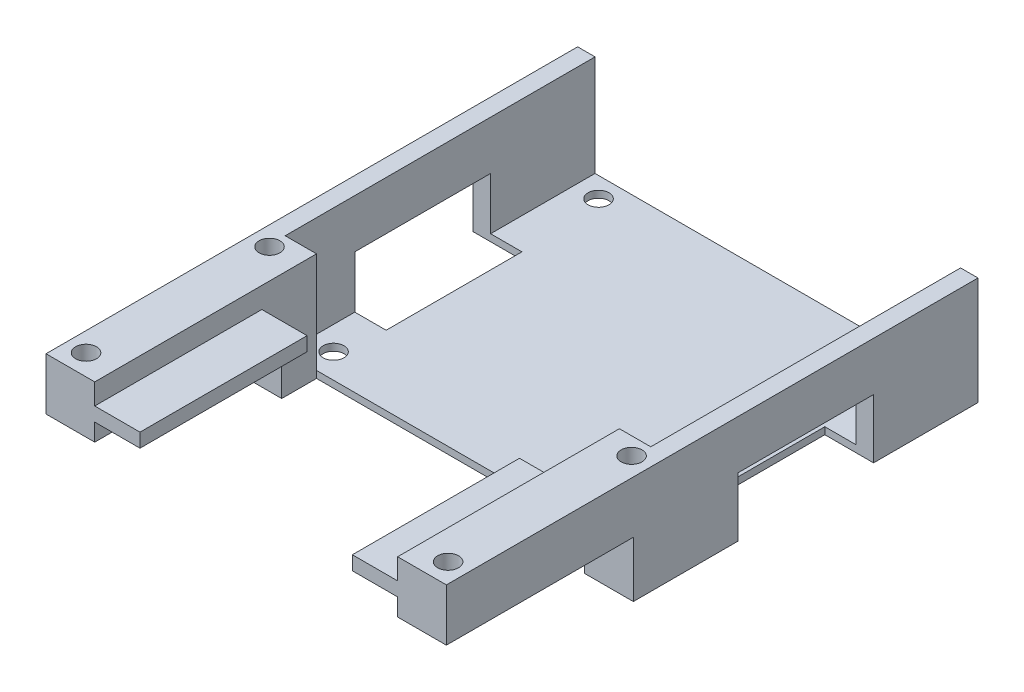
SolidWorks part; units mm, degrees
ref_plane "Front Plane" through (0, 0, 0) normal (0, 0, 1) x (1, 0, 0)
ref_plane "Top Plane" through (0, 0, 0) normal (0, 1, 0) x (1, 0, 0)
ref_plane "Right Plane" through (0, 0, 0) normal (1, 0, 0) x (0, 0, -1)
sketch "Sketch1" plane through (0, 0, 0) normal (0, 1, 0) x (1, 0, 0)
  line L0 (0, 0) -> (0, 76.35) construction
  line L1 (-28.75, 76.35) -> (28.75, 76.35)
  line L2 (28.75, 76.35) -> (28.75, 0)
  line L3 (28.75, 0) -> (21.75, 0)
  line L4 (21.75, 0) -> (21.75, 31.85)
  line L5 (21.75, 31.85) -> (-21.75, 31.85)
  line L6 (-21.75, 31.85) -> (-21.75, 0)
  line L7 (-21.75, 0) -> (-28.75, 0)
  line L8 (-28.75, 0) -> (-28.75, 76.35)
  line L9 (-26.25, 76.35) -> (-26.25, 31.85)
  line L14 (-26.25, 31.85) -> (-21.75, 31.85)
  line L15 (26.25, 76.35) -> (26.25, 31.85)
  line L16 (26.25, 31.85) -> (21.75, 31.85)
  line L17 (28.75, 74.35) -> (30.25, 74.35)
  line L18 (-28.75, 41.35) -> (-26.25, 41.35)
  line L19 (-28.75, 41.35) -> (-28.75, 53.35)
  line L20 (-28.75, 53.35) -> (-26.25, 53.35)
  line L21 (-26.25, 41.35) -> (-26.25, 53.35)
  line L22 (30.25, 68.35) -> (28.75, 68.35)
  line L23 (-30.25, 68.35) -> (-28.75, 68.35)
  line L24 (-28.75, 74.35) -> (-30.25, 74.35)
  arc A0 (30.25, 68.35) -> (30.25, 74.35) centre (30.25, 71.35) ccw
  arc A1 (-30.25, 68.35) -> (-30.25, 74.35) centre (-30.25, 71.35) cw
  point P10 (0, 76.35)
  point P16 (-27.5, 41.35)
  point P17 (-22.85, 73.45)
  point P18 (22.85, 73.45)
  point P23 (22.85, 35.4)
  point P24 (-22.85, 35.4)
  point P25 (26, 3)
  point P26 (26, 29.35)
  point P27 (-26, 29.35)
  point P28 (-26, 3)
  point P40 (30.25, 71.35)
  point P41 (-30.25, 71.35)
  dimension "D16" = 3
  dimension "D1" = 2.5
  dimension "D2" = 7
  dimension "D3" = 43.5
  dimension "D4" = 31.85
  dimension "D5" = 44.5
  dimension "D6" = 23
  dimension "D7" = 12
  dimension "D8" = 22.85
  dimension "D9" = 38.05
  dimension "D10" = 2.9
  dimension "D11" = 52
  dimension "D12" = 52
  dimension "D13" = 47
  dimension "D14" = 3
  dimension "D15" = 1.5
  dimension "D17" = 2
extrude "Boss-Extrude1" add sketch "Sketch1" along normal blind 1 contours L5 L0 L1 L9 L14 | L0 L5 L16 L15 L1 region at (-13.125, 0, -54.1) region at (13.125, 0, -54.1)
extrude "Boss-Extrude2" add sketch "Sketch1<3>" along normal blind 15.5 contours L18 L8 L7 L6 L14 L9 | L8 L20 L9 L1 | L15 L16 L4 L3 L2 L1 | L20 L8 L18 L9 region at (-27.5, 0, -64.85) region at (25.999, 0, -28.6329) region at (-27.5, 0, -47.35) region at (-25.4666, 0, -17.9154)
sketch "Sketch1<3>" plane through (0, 0, 0) normal (0, 1, 0) x (1, 0, 0) same geometry as "Sketch1"
hole_wizard "Ø3.0 (3) Diameter Hole1" positions "Sketch4" profile "Sketch5" hole size "Ø3.0" standard "ANSI Metric" end condition through all
sketch "Sketch4" plane through (0, 0, 0) normal (0, -1, 0) x (-1, 0, 0)
  point P0 (-22.85, 73.45)
  point P3 (22.85, 73.45)
  point P6 (26, 29.35)
  point P9 (22.85, 35.4)
  point P12 (-22.85, 35.4)
  point P15 (-26, 29.35)
  point P18 (-26, 3)
  point P21 (26, 3)
  point P24 (-30.25, 71.35)
  point P27 (30.25, 71.35)
sketch "Sketch5" plane through (22.85, 0, -73.45) normal (1, 0, 0) x (0, 0, -1)
  line L0 (0, 0) -> (0, 15.5)
  line L1 (0, 15.5) -> (1.5, 15.5)
  line L2 (1.5, 15.5) -> (1.5, 0)
  line L5 (1.5, 0) -> (0, 0)
  line L11 (0, -6.35) -> (0, 107.95) construction
  dimension "Thru Hole Dia." = 3
  dimension "Thru Hole Depth" = 15.5
sketch "Sketch6" plane through (0, 0, 0) normal (0, 0, 1) x (1, 0, 0)
  line L0 (-21.75, 15.5) -> (-21.75, 0) construction
  line L5 (0, -1.6497) -> (0, 21.9352) construction
  line L6 (-21.75, 10.5) -> (-15.25, 10.5)
  line L7 (-21.75, 10.5) -> (-21.75, 12.5)
  line L8 (-21.75, 12.5) -> (-15.25, 12.5)
  line L9 (-15.25, 10.5) -> (-15.25, 12.5)
  line L10 (-28.75, 15.5) -> (-28.75, 0) construction
  line L11 (-20.25, 10.5) -> (-21.75, 10.5)
  line L12 (-20.25, 10.5) -> (-20.25, 8)
  line L13 (-20.25, 8) -> (-21.75, 8)
  line L14 (-21.75, 10.5) -> (-21.75, 8)
  line L15 (-21.75, 0) -> (-28.75, 0)
  line L16 (-21.75, 0) -> (-21.75, 8)
  line L17 (-21.75, 8) -> (-28.75, 8)
  line L18 (-28.75, 0) -> (-28.75, 8)
  line L19 (28.75, 0) -> (28.75, 8)
  line L20 (21.75, 8) -> (28.75, 8)
  line L21 (21.75, 0) -> (21.75, 8)
  line L22 (21.75, 0) -> (28.75, 0)
  line L23 (21.75, 10.5) -> (21.75, 8)
  line L24 (20.25, 8) -> (21.75, 8)
  line L25 (20.25, 10.5) -> (20.25, 8)
  line L26 (20.25, 10.5) -> (21.75, 10.5)
  line L27 (15.25, 10.5) -> (15.25, 12.5)
  line L28 (21.75, 12.5) -> (15.25, 12.5)
  line L29 (21.75, 10.5) -> (21.75, 12.5)
  line L30 (21.75, 10.5) -> (15.25, 10.5)
  line L31 (-21.75, 15.5) -> (-28.75, 15.5) construction
  line M21 (21.75, 0) -> (28.75, 0)
  line M22 (28.75, 0) -> (28.75, 15.5)
  line M24 (21.75, 15.5) -> (21.75, 0)
  dimension "D1" = 6.5
  dimension "D2" = 3
  dimension "D3" = 2
  dimension "D4" = 2.5
  dimension "D5" = 1.5
extrude "Boss-Extrude3" add sketch "Sketch6" against normal blind 24 contours L30 L26 L28 L27 M24 | L6 L9 L8 L7 region at (-18.5, 11.5, 0) region at (18.5, 11.5, 0)
extrude "Cut-Extrude1" cut sketch "Sketch6<4>" against normal blind 26.85 contours L18 L15 L16 L17 | L20 M24 M21 M22 region at (-25.25, 4, 0) region at (25.25, 4, 0)
sketch "Sketch6<4>" plane through (0, 0, 0) normal (0, 0, 1) x (1, 0, 0) same geometry as "Sketch6"
sketch "Sketch8" plane through (0, 0, 0) normal (0, -1, 0) x (1, 0, 0)
  line L0 (0, 17.5937) -> (0, -89.2896) construction
  line L1 (-28.75, -61.35) -> (-21.75, -61.35)
  line L2 (-28.75, -61.35) -> (-28.75, -41.85)
  line L3 (-28.75, -41.85) -> (-21.75, -41.85)
  line L4 (-21.75, -61.35) -> (-21.75, -41.85)
  line L6 (-28.75, -76.35) -> (28.75, -76.35) construction
  line L8 (21.75, -61.35) -> (21.75, -41.85)
  line L9 (28.75, -41.85) -> (21.75, -41.85)
  line L10 (28.75, -61.35) -> (28.75, -41.85)
  line L11 (28.75, -61.35) -> (21.75, -61.35)
  line L12 (-28.75, -26.85) -> (-28.75, -76.35) construction
  dimension "D1" = 15
  dimension "D2" = 7
  dimension "D3" = 19.5
extrude "Cut-Extrude2" cut sketch "Sketch8" against normal blind 8.5
sketch "Sketch9" plane through (0, 0, 0) normal (0, -1, 0) x (1, 0, 0)
  line L0 (-3.426, -64.9209) -> (-1.4298, -53.6)
  line L1 (-1.4298, -53.6) -> (-9.4298, -53.6)
  line L2 (-9.4298, -53.6) -> (3.426, -38.2791)
  line L3 (3.426, -38.2791) -> (1.4298, -49.6)
  line L4 (1.4298, -49.6) -> (9.4298, -49.6)
  line L5 (9.4298, -49.6) -> (-3.426, -64.9209)
  line L6 (-1.4298, -53.6) -> (1.4298, -49.6) construction
  line L7 (-21.75, -61.35) -> (-21.75, -41.85) construction
  point P2 (0, -51.6)
  point P9 (-21.75, -51.6)
  dimension "D1" = 50
  dimension "D2" = 50
  dimension "D3" = 30
  dimension "D4" = 30
  dimension "D5" = 4
  dimension "D6" = 20
  dimension "D7" = 20
  dimension "D8" = 8
extrude "Cut-Extrude3" cut sketch "Sketch9" against normal blind 0.3
equation "\"D1@Boss-Extrude2\"=16.000000mm-0.5"
equation "\"D7@Sketch9\"=\"D6@Sketch9\""
equation "\"D2@Sketch9\"=\"D1@Sketch9\""
equation "\"D4@Sketch9\"=\"D3@Sketch9\""
